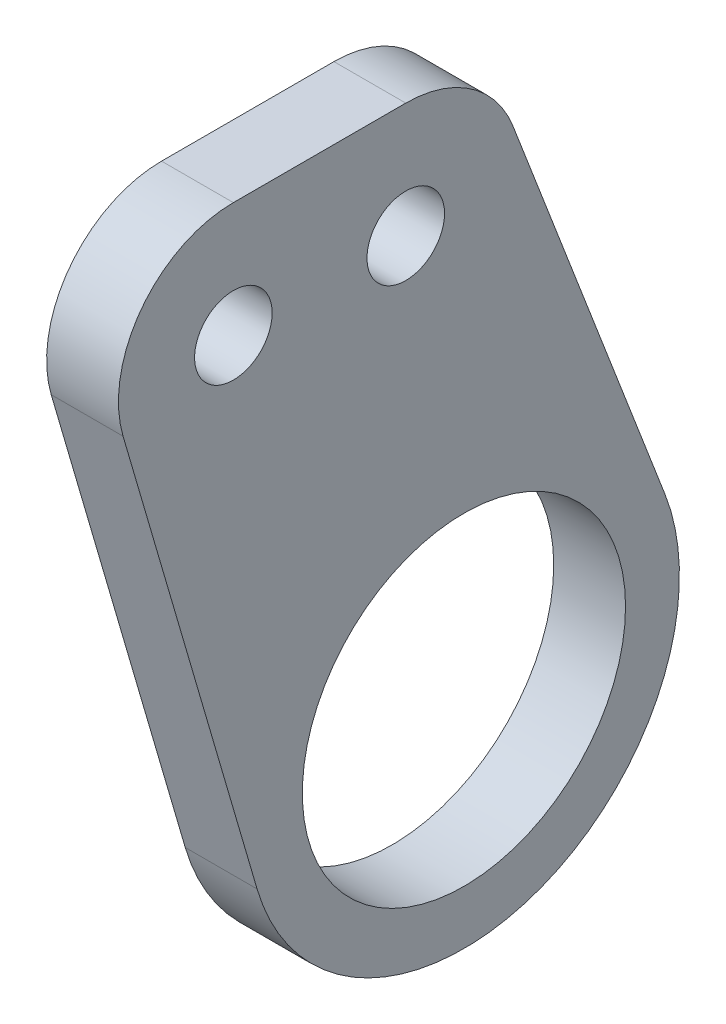
SolidWorks part; units mm, degrees
ref_plane "Front Plane" through (0, 0, 0) normal (0, 0, 1) x (1, 0, 0)
ref_plane "Top Plane" through (0, 0, 0) normal (0, 1, 0) x (1, 0, 0)
ref_plane "Right Plane" through (0, 0, 0) normal (1, 0, 0) x (0, 0, -1)
sketch "Sketch1" plane through (0, 0, 0) normal (1, 0, 0) x (0, 0, -1)
  line L0 (14.2875, 0) -> (14.2875, 38.1) construction
  line L1 (14.2875, 38.1) -> (-20.3835, 38.1) construction
  line L2 (-20.3835, 48.26) -> (-5.1435, 48.26)
  line L3 (-30.1364, 35.2529) -> (-18.2867, -5.3384)
  line L4 (4.338, 41.7507) -> (17.7778, 6.845)
  circle A0 centre (0, 0) radius 14.2875
  circle A1 centre (-20.3835, 38.1) radius 3.429
  circle A2 centre (-5.1435, 38.1) radius 3.429
  arc A3 (-20.3835, 48.26) -> (-30.1364, 35.2529) centre (-20.3835, 38.1) ccw
  arc A4 (4.338, 41.7507) -> (-5.1435, 48.26) centre (-5.1435, 38.1) ccw
  arc A5 (-18.2867, -5.3384) -> (17.7778, 6.845) centre (0, 0) ccw
  dimension "D1" = 28.575
  dimension "D2" = 15.24
  dimension "D3" = 6.858
  dimension "D6" = 10.16
  dimension "D7" = 38.1
  dimension "D4" = 34.671
  dimension "D5" = 38.1
extrude "Boss-Extrude1" add sketch "Sketch1" along normal blind 3.175 and the other way blind 3.175
